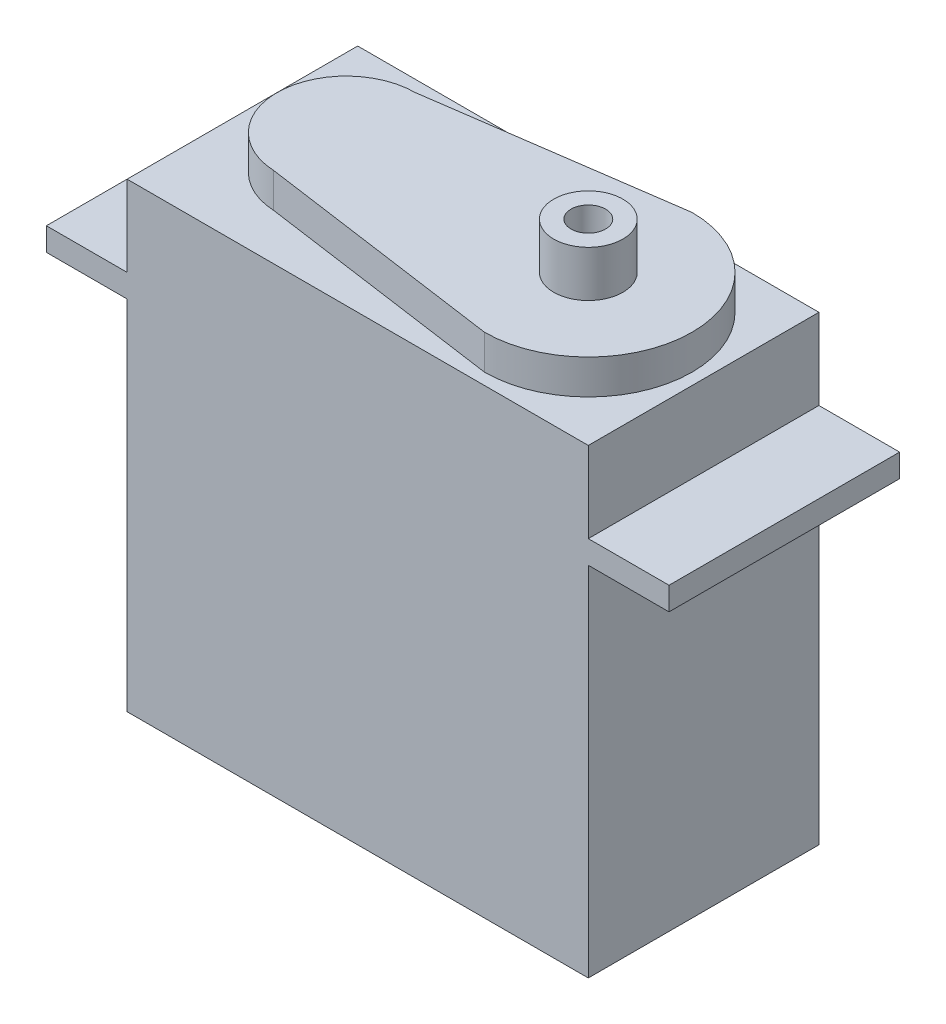
SolidWorks part; units mm, degrees
ref_plane "前视基准面" through (0, 0, 0) normal (0, 0, 1) x (1, 0, 0)
ref_plane "上视基准面" through (0, 0, 0) normal (0, 1, 0) x (1, 0, 0)
ref_plane "右视基准面" through (0, 0, 0) normal (1, 0, 0) x (0, 0, -1)
sketch "草图1" plane through (0, 0, 0) normal (0, 0, 1) x (1, 0, 0)
  line L1 (-20, 20) -> (20, 20)
  line L2 (-20, 20) -> (-20, -20)
  line L3 (-20, -20) -> (20, -20)
  line L4 (20, 20) -> (20, -20)
  line L5 (-20, 20) -> (20, -20) construction
  line L6 (-20, -20) -> (20, 20) construction
  point P0 (0, 0)
  dimension "D1" = 40
  dimension "D2" = 40
extrude "凸台-拉伸1" add sketch "草图1" along normal blind 20
sketch "草图2" plane through (0, 20, 0) normal (0, 1, 0) x (1, 0, 0)
  line L3 (20, -20) -> (20, 0) construction
  line L4 (-20, -20) -> (-20, 0) construction
  line L5 (10, -1) -> (-11, -4)
  line L6 (-11.2901, -15.993) -> (10, -19)
  arc A0 (10, -19) -> (10, -1) centre (10, -10) ccw
  arc A1 (-11, -4) -> (-11.2901, -15.993) centre (-11, -10) ccw
  point P7 (19, -10)
  point P10 (10, -10)
  point P13 (-17, -10)
  point P16 (-11, -10)
  dimension "D2" = 1
  dimension "D3" = 9
  dimension "D4" = 3
  dimension "D5" = 6
extrude "凸台-拉伸2" add sketch "草图2" along normal blind 3 contours L5 A1 L6 A0
sketch "草图5" plane through (0, 23, 0) normal (0, 1, 0) x (1, 0, 0)
  line L0 (-23.0759, -10) -> (28.1102, -10) construction
  line L1 (20, 0) -> (-20, 0) construction
  line L2 (20, -20) -> (20, 0) construction
  circle A0 centre (10, -10) radius 3
  circle A1 centre (10, -10) radius 1.5
  point P4 (10, -10)
  dimension "D1" = 10
  dimension "D2" = 10
extrude "凸台-拉伸3" add sketch "草图5" along normal blind 4
sketch "草图6" plane through (0, 0, 0) normal (0, 0, -1) x (-1, 0, 0)
  line L0 (-20, -20) -> (-20, 20) construction
  line L1 (-20, 13) -> (-27, 13)
  line L2 (-20, 13) -> (-20, 11)
  line L3 (-20, 11) -> (-27, 11)
  line L4 (-27, 13) -> (-27, 11)
  line L5 (-20, 20) -> (20, 20) construction
  line L6 (20, 20) -> (20, -20) construction
  line L7 (20, 13) -> (27, 13)
  line L8 (20, 13) -> (20, 11)
  line L9 (20, 11) -> (27, 11)
  line L10 (27, 13) -> (27, 11)
  dimension "D1" = 7
  dimension "D2" = 7
  dimension "D3" = 2
  dimension "D4" = 7
  dimension "D5" = 2
  dimension "D6" = 7
extrude "凸台-拉伸4" add sketch "草图6" against normal blind 20
